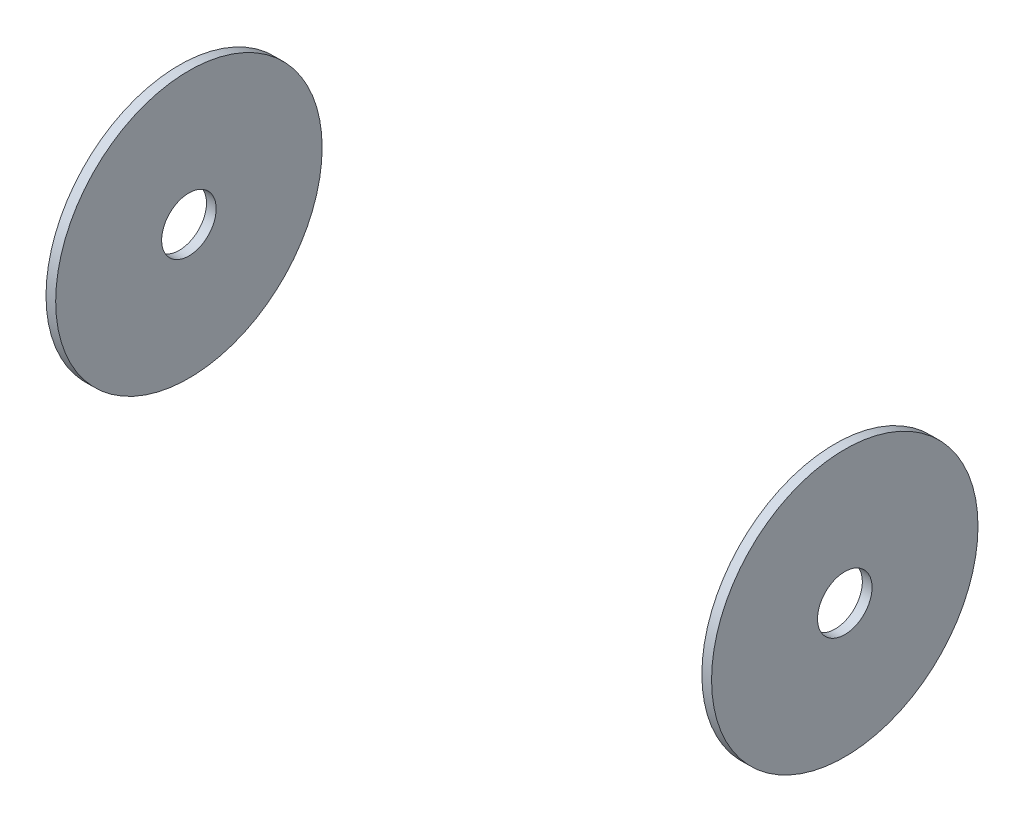
SolidWorks part; units mm, degrees
material "Titanium"
ref_plane "Front Plane" through (0, 0, 0) normal (0, 0, 1) x (1, 0, 0)
ref_plane "Top Plane" through (0, 0, 0) normal (0, 1, 0) x (1, 0, 0)
ref_plane "Right Plane" through (0, 0, 0) normal (1, 0, 0) x (0, 0, -1)
sketch "Sketch1" plane through (50.05, 0, 0) normal (1, 0, 0) x (0, 0, -1)
  circle A0 centre (-175.4, 26.9875) radius 20.6375
  arc A1 (-194.0448, 35.8349) -> (-195.7234, 23.4009) centre (-175.4, 26.9875) ccw construction
  circle A2 centre (-175.4, 26.9875) radius 4.2228
  dimension "D1" = 8.4455
extrude "Boss-Extrude1" add sketch "Sketch1" along normal blind 1.5
mirror "Mirror2" about plane through (0, 0, 0) normal (1, 0, 0) of bodies 101
equation "\"weapon shaft threads\"= 5 / 16"
equation "\"D1@Sketch1\"=\"weapon shaft threads\" + .02in"
equation "\"D1@Boss-Extrude1\"=1.5mm"
